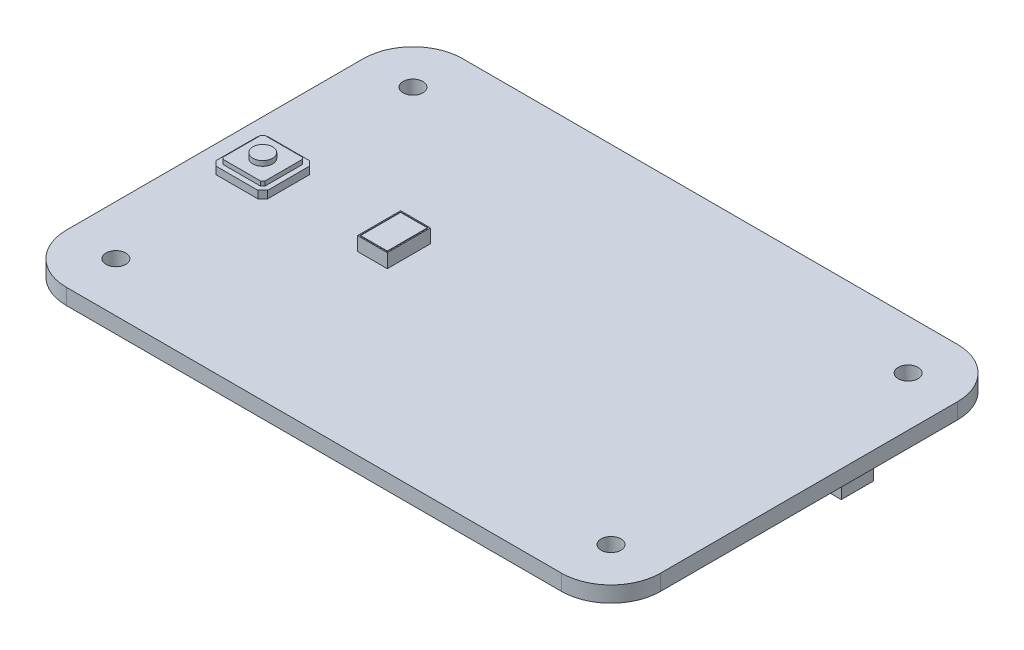
SolidWorks part; units mm, degrees
ref_plane "Front Plane" through (0, 0, 0) normal (0, 0, 1) x (1, 0, 0)
ref_plane "Top Plane" through (0, 0, 0) normal (0, 1, 0) x (1, 0, 0)
ref_plane "Right Plane" through (0, 0, 0) normal (1, 0, 0) x (0, 0, -1)
sketch "Sketch1" plane through (0, 0, 0) normal (0, 1, 0) x (1, 0, 0)
  line L1 (-30, 20) -> (30, 20)
  line L2 (-30, 20) -> (-30, -20)
  line L3 (-30, -20) -> (30, -20)
  line L4 (30, 20) -> (30, -20)
  dimension "D1" = 40
  dimension "D2" = 60
  dimension "D3" = 30
  dimension "D4" = 20
extrude "Boss-Extrude1" add sketch "Sketch1" along normal blind 1.6
sketch "Sketch2" plane through (0, 1.6, 0) normal (0, 1, 0) x (1, 0, 0)
  line L0 (-7.2175, 0) -> (11.6655, 0) construction
  line L1 (-30, 20) -> (-30, -20) construction
  line L2 (30, 20) -> (-30, 20) construction
  circle A0 centre (-25, 15) radius 1
  circle A1 centre (25, 15) radius 1
  circle A2 centre (25, -15) radius 1
  circle A3 centre (-25, -15) radius 1
  dimension "D3" = 5
  dimension "D4" = 2
  dimension "D1" = 5
  dimension "D2" = 50
extrude "Cut-Extrude1" cut sketch "Sketch2" against normal through all
fillet "Fillet1" radius 5 4 edges at (-30, 0.8, 20) (30, 0.8, 20) (30, 0.8, -20) (-30, 0.8, -20)
sketch "Sketch4" plane through (0, 1.6, 0) normal (0, 1, 0) x (1, 0, 0)
  line L0 (-31.7, 4.47) -> (-29.9, 4.47) construction
  line L1 (-29.5, 4.47) -> (-28.7, 4.47)
  line L2 (-29.5, 4.47) -> (-29.5, 4.17)
  line L3 (-29.5, 4.17) -> (-28.7, 4.17)
  line L4 (-28.7, 4.47) -> (-28.7, 4.17)
  line L5 (-31.4, 4.17) -> (-25.05, 4.17) construction
  line L7 (-29.5, 4.47) -> (-29.5, 4.17) construction
  line L8 (-28.7, 4.17) -> (-28.7, 4.47) construction
  line L9 (-25.47, 4.47) -> (-25.47, 4.17) construction
  line L10 (-25.47, 4.47) -> (-24.37, 4.47)
  line L11 (-25.47, 4.47) -> (-25.47, 4.17)
  line L12 (-25.47, 4.17) -> (-24.37, 4.17)
  line L13 (-24.37, 4.47) -> (-24.37, 4.17)
  line L14 (-24.37, 4.47) -> (-24.37, 4.17) construction
  line L15 (-30, 0) -> (-33.939, 0) construction
  line L16 (-30, 15) -> (-30, -15) construction
  line L17 (-24.37, -4.47) -> (-24.37, -4.17)
  line L18 (-25.47, -4.17) -> (-24.37, -4.17)
  line L19 (-25.47, -4.47) -> (-25.47, -4.17)
  line L20 (-25.47, -4.47) -> (-24.37, -4.47)
  line L21 (-28.7, -4.47) -> (-28.7, -4.17)
  line L22 (-29.5, -4.17) -> (-28.7, -4.17)
  line L23 (-29.5, -4.47) -> (-29.5, -4.17)
  line L24 (-29.5, -4.47) -> (-28.7, -4.47)
extrude "Cut-Extrude2" cut sketch "Sketch4" against normal through all from offset 0.5 offset against normal yes
sketch "Sketch5" plane through (0, 0, 0) normal (0, -1, 0) x (1, 0, 0)
  line L1 (-1.7, 5.7) -> (4.3, 5.7)
  line L2 (-1.7, 5.7) -> (-1.7, -5.7)
  line L3 (-1.7, -5.7) -> (4.3, -5.7)
  line L4 (4.3, 5.7) -> (4.3, -5.7)
  line L5 (-30, -15) -> (-30, 15) construction
  dimension "D1" = 11.4
  dimension "D2" = 5.7
  dimension "D3" = 6
  dimension "D4" = 34.3
extrude "Boss-Extrude2" add sketch "Sketch5" along normal blind 2 separate body
sketch "Sketch6" plane through (0, -2, 0) normal (0, -1, 0) x (1, 0, 0)
  line L0 (0, 0) -> (17.1285, 0) construction
  line L1 (3.8, 5.7) -> (3.8, 5.2)
  line L2 (4.3, 5.7) -> (-1.7, 5.7) construction
  line L3 (3.8, 5.2) -> (1.95, 5.2)
  line L4 (1.95, 5.2) -> (1.95, 4.2)
  line L5 (1.95, 4.2) -> (2.2, 4.2)
  line L6 (2.2, 4.2) -> (2.2, -4.2)
  line L7 (4.3, -5.7) -> (4.3, 5.7) construction
  line L8 (3.8, -5.7) -> (3.8, -5.2)
  line L9 (3.8, -5.2) -> (1.95, -5.2)
  line L10 (1.95, -5.2) -> (1.95, -4.2)
  line L11 (1.95, -4.2) -> (2.2, -4.2)
  line L12 (3.8, 5.2) -> (3.8, -5.2)
  line L13 (3.8649, 5.7) -> (3.8649, -5.7)
  line L14 (-1.7, -5.7) -> (4.3, -5.7) construction
  line L15 (3.8649, -5.7) -> (3.8, -5.7)
  line L16 (3.8, 5.7) -> (3.8649, 5.7)
  point P18 (2.2, 0)
  line M8 (-1.7, -5.7) -> (4.3, -5.7)
  line M10 (4.3, 5.7) -> (-1.7, 5.7)
  dimension "D1" = 0.5
  dimension "D2" = 1.85
  dimension "D3" = 1
  dimension "D4" = 0.25
  dimension "D5" = 0.5
extrude "Cut-Extrude3" cut sketch "Sketch6" against normal blind 0.5 contours L6 L0 L12 L3 L4 L5 | L0 L6 L11 L10 L9 L12 region at (2.973, -2, 2.6613) region at (2.973, -2, -2.6613)
extrude "Cut-Extrude4" cut sketch "Sketch6<3>" against normal blind 1.75 contours L12 L0 L13 L1 M10 | L0 L12 L8 L13 M8 region at (3.8325, -2, 2.85) region at (3.8325, -2, -2.85)
sketch "Sketch6<3>" plane through (0, -2, 0) normal (0, -1, 0) x (1, 0, 0) same geometry as "Sketch6"
sketch "Sketch7" plane through (0, 1.6, 0) normal (0, 1, 0) x (1, 0, 0)
  line L0 (-30, 15) -> (-30, -15) construction
  line L1 (-27.27, 2.6) -> (-23.07, 2.6)
  line L2 (-27.77, 2.1) -> (-27.77, -2.1)
  line L3 (-27.27, -2.6) -> (-23.07, -2.6)
  line L4 (-22.57, 2.1) -> (-22.57, -2.1)
  line L5 (-27.77, 2.6) -> (-22.57, -2.6) construction
  line L6 (-27.77, -2.6) -> (-22.57, 2.6) construction
  line L8 (-27.77, 2.1) -> (-27.27, 2.6)
  line L9 (-23.07, 2.6) -> (-22.57, 2.1)
  line L10 (-22.57, -2.1) -> (-23.07, -2.6)
  line L11 (-27.77, -2.1) -> (-27.27, -2.6)
  point P0 (-25.17, 0)
  dimension "D1" = 4.83
  dimension "D2" = 5.2
  dimension "D3" = 5.2
extrude "Boss-Extrude3" add sketch "Sketch7" along normal blind 0.75 separate body
sketch "Sketch8" plane through (0, 2.35, 0) normal (0, 1, 0) x (1, 0, 0)
  line L8 (-25.17, 2.1) -> (-25.17, -1.5934) construction
  line L16 (-27.0629, 2.1) -> (-27.27, 1.8929)
  line L17 (-27.27, 1.8929) -> (-27.27, -1.8929)
  line L18 (-27.27, -1.8929) -> (-27.0629, -2.1)
  line L19 (-27.0629, -2.1) -> (-23.2771, -2.1)
  line L20 (-23.2771, -2.1) -> (-23.07, -1.8929)
  line L21 (-23.07, -1.8929) -> (-23.07, 1.8929)
  line L22 (-23.07, 1.8929) -> (-23.2771, 2.1)
  line L23 (-23.2771, 2.1) -> (-27.0629, 2.1)
  line L24 (-27.0629, 2.1) -> (-27.27, 1.8929)
  line L25 (-27.27, 1.8929) -> (-27.27, -1.8929)
  line L26 (-27.27, -1.8929) -> (-27.0629, -2.1)
  line L27 (-27.0629, -2.1) -> (-23.2771, -2.1)
  line L28 (-23.2771, -2.1) -> (-23.07, -1.8929)
  line L29 (-23.07, -1.8929) -> (-23.07, 1.8929)
  line L30 (-23.07, 1.8929) -> (-23.2771, 2.1)
  line L31 (-23.2771, 2.1) -> (-27.0629, 2.1)
  circle A0 centre (-25.17, 0) radius 1
  dimension "D2" = 2
  dimension "D1" = 0.5
extrude "Boss-Extrude4" add sketch "Sketch8" along normal blind 0.45 contours L30 L31 A0 L24 L25 L26 L27 L28 L29 | A0 region at (-25.17, 2.35, -2.0406)
sketch "Sketch9" plane through (0, 1.6, 0) normal (0, 1, 0) x (1, 0, 0)
  line L1 (-13.42, 2.175) -> (-10.42, 2.175)
  line L2 (-13.42, 2.175) -> (-13.42, -2.175)
  line L3 (-13.42, -2.175) -> (-10.42, -2.175)
  line L4 (-10.42, 2.175) -> (-10.42, -2.175)
  line L5 (-13.42, 2.175) -> (-10.42, -2.175) construction
  line L6 (-13.42, -2.175) -> (-10.42, 2.175) construction
  line L7 (-22.57, -2.1) -> (-22.57, 2.1) construction
  point P0 (-11.92, 0)
  dimension "D1" = 4.35
  dimension "D2" = 3
  dimension "D3" = 9.15
extrude "Boss-Extrude6" add sketch "Sketch9" along normal blind 1.4 separate body
sketch "Sketch10" plane through (0, 3, 0) normal (0, 1, 0) x (1, 0, 0)
  line L8 (-10.52, -2.075) -> (-10.52, 2.075)
  line L9 (-10.52, 2.075) -> (-13.32, 2.075)
  line L10 (-13.32, 2.075) -> (-13.32, -2.075)
  line L11 (-13.32, -2.075) -> (-10.52, -2.075)
  line L12 (-10.52, -2.075) -> (-10.52, 2.075)
  line L13 (-10.52, 2.075) -> (-13.32, 2.075)
  line L14 (-13.32, 2.075) -> (-13.32, -2.075)
  line L15 (-13.32, -2.075) -> (-10.52, -2.075)
  dimension "D1" = 0.1
extrude "Cut-Extrude5" cut sketch "Sketch10" against normal blind 0.1
sketch "Sketch11" plane through (0, 2.9, 0) normal (0, 1, 0) x (1, 0, 0)
  line L8 (-13.27, -2.025) -> (-10.57, -2.025)
  line L9 (-10.57, -2.025) -> (-10.57, 2.025)
  line L10 (-10.57, 2.025) -> (-13.27, 2.025)
  line L11 (-13.27, 2.025) -> (-13.27, -2.025)
  line L12 (-13.27, -2.025) -> (-10.57, -2.025)
  line L13 (-10.57, -2.025) -> (-10.57, 2.025)
  line L14 (-10.57, 2.025) -> (-13.27, 2.025)
  line L15 (-13.27, 2.025) -> (-13.27, -2.025)
  dimension "D1" = 0.05
extrude "Boss-Extrude7" add sketch "Sketch11" along normal blind 0.1
sketch "Sketch13" plane through (0, 0, 0) normal (0, -1, 0) x (1, 0, 0)
  line L0 (25, -20) -> (-25, -20) construction
  line L1 (-16.5, -15) -> (-12.5, -15)
  line L2 (-16.5, -15) -> (-16.5, -19)
  line L3 (-16.5, -19) -> (-12.5, -19)
  line L4 (-12.5, -15) -> (-12.5, -19)
  line L5 (-16.5, -15) -> (-12.5, -19) construction
  line L6 (-16.5, -19) -> (-12.5, -15) construction
  line L7 (-30, -15) -> (-30, 15) construction
  point P0 (-14.5, -17)
  dimension "D1" = 4
  dimension "D2" = 4
  dimension "D3" = 1
  dimension "D4" = 17.5
extrude "Boss-Extrude8" add sketch "Sketch13" along normal blind 1.75 separate body
sketch "Sketch14" plane through (0, 0, 0) normal (0, -1, 0) x (1, 0, 0)
  line L0 (4.3, -5.7) -> (4.3, 5.7) construction
  line L1 (-0.65, -9.7) -> (4.55, -9.7)
  line L2 (-0.65, -9.7) -> (-0.65, -15.1)
  line L3 (-0.65, -15.1) -> (4.55, -15.1)
  line L4 (4.55, -9.7) -> (4.55, -15.1)
  line L5 (-1.7, -5.7) -> (3.8, -5.7) construction
  dimension "D1" = 0.25
  dimension "D2" = 5.4
  dimension "D3" = 5.2
  dimension "D4" = 4
extrude "Boss-Extrude9" add sketch "Sketch14" along normal blind 1.5 separate body
sketch "Sketch15" plane through (0, 0, 0) normal (0, -1, 0) x (1, 0, 0)
  line L0 (4.3, -5.7) -> (4.3, 5.7) construction
  line L1 (-9.2, 13.5) -> (-5.4, 13.5)
  line L2 (-9.2, 13.5) -> (-9.2, 8.5)
  line L3 (-9.2, 8.5) -> (-5.4, 8.5)
  line L4 (-5.4, 13.5) -> (-5.4, 8.5)
  line L5 (-1.7, -5.7) -> (3.8, -5.7) construction
  dimension "D1" = 3.8
  dimension "D2" = 5
  dimension "D3" = 13.5
  dimension "D4" = 19.2
extrude "Boss-Extrude10" add sketch "Sketch15" along normal blind 1.5 separate body
sketch "Sketch16" plane through (0, 0, 0) normal (0, -1, 0) x (1, 0, 0)
  line L0 (30, 15) -> (30, -15) construction
  line L1 (28.1, -3.5) -> (29.75, -3.5)
  line L2 (28.1, -3.5) -> (28.1, -6.75)
  line L3 (28.1, -6.75) -> (29.75, -6.75)
  line L4 (29.75, -3.5) -> (29.75, -6.75)
  line L5 (25, -20) -> (-25, -20) construction
  dimension "D1" = 0.25
  dimension "D2" = 1.65
  dimension "D3" = 3.25
  dimension "D4" = 13.25
extrude "Boss-Extrude11" add sketch "Sketch16" along normal blind 1.35 separate body
sketch "Sketch17" plane through (0, 2.8, 0) normal (0, 1, 0) x (1, 0, 0)
  line L1 (-25.17, 2.1) -> (-25.17, -2.1) construction
  line L2 (-23.2771, 2.1) -> (-27.0629, 2.1) construction
  line L3 (-27.0629, -2.1) -> (-23.2771, -2.1) construction
  line L4 (-27.27, 0) -> (-23.07, 0) construction
  line L5 (-27.27, 1.8929) -> (-27.27, -1.8929) construction
  line L6 (-23.07, -1.8929) -> (-23.07, 1.8929) construction
  circle A0 centre (-25.17, 0) radius 1
  dimension "D1" = 2
extrude "Boss-Extrude12" add sketch "Sketch17" along normal blind 0.5
sketch "Sketch18" plane through (0, 3.3, 0) normal (0, 1, 0) x (1, 0, 0)
  line L0 (-25.17, 0) -> (-27.3592, 2.1092) construction
sketch "Sketch19" plane through (0, 0, 0) normal (0, -1, 0) x (1, 0, 0)
  line L1 (-29.2, 7.17) -> (-28.3, 7.17)
  line L2 (-29.2, 7.17) -> (-29.2, 5.47)
  line L3 (-29.2, 5.47) -> (-28.3, 5.47)
  line L4 (-28.3, 7.17) -> (-28.3, 5.47)
  line L5 (-27.7, 7.17) -> (-26.8, 7.17)
  line L6 (-27.7, 7.17) -> (-27.7, 5.47)
  line L7 (-27.7, 5.47) -> (-26.8, 5.47)
  line L8 (-26.8, 7.17) -> (-26.8, 5.47)
  line L9 (-30, -15) -> (-30, 15) construction
  line L10 (-19.0449, 0) -> (-46.6157, 0) construction
  line L11 (-27.7, -5.47) -> (-26.8, -5.47)
  line L12 (-26.8, -7.17) -> (-26.8, -5.47)
  line L13 (-27.7, -7.17) -> (-26.8, -7.17)
  line L14 (-27.7, -7.17) -> (-27.7, -5.47)
  line L15 (-29.2, -5.47) -> (-28.3, -5.47)
  line L16 (-28.3, -7.17) -> (-28.3, -5.47)
  line L17 (-29.2, -7.17) -> (-28.3, -7.17)
  line L18 (-29.2, -7.17) -> (-29.2, -5.47)
  line L19 (-29.5, 4.47) -> (-28.7, 4.47) construction
  line L20 (-29.5, 4.32) -> (-32.4644, 4.32) construction
  line L21 (-29.5, 4.17) -> (-29.5, 4.47) construction
  dimension "D1" = 1.7
  dimension "D2" = 1.7
  dimension "D3" = 0.9
  dimension "D4" = 0.9
  dimension "D5" = 1
  dimension "D6" = 0.6
  dimension "D7" = 0.8
extrude "Boss-Extrude13" add sketch "Sketch19" along normal blind 0.15 separate body
sketch "Sketch20" plane through (0, -0.15, 0) normal (0, -1, 0) x (1, 0, 0)
  line L0 (-29.2, 7.17) -> (-29.2, 5.47) construction
  line L1 (-29.2, 6.92) -> (-28.3, 6.92)
  line L2 (-29.2, 6.92) -> (-29.2, 5.72)
  line L3 (-29.2, 5.72) -> (-28.3, 5.72)
  line L4 (-28.3, 6.92) -> (-28.3, 5.72)
  line L5 (-28.3, 5.47) -> (-28.3, 7.17) construction
  line L6 (-27.7, 7.17) -> (-27.7, 5.47) construction
  line L7 (-27.7, 6.92) -> (-26.8, 6.92)
  line L8 (-27.7, 6.92) -> (-27.7, 5.72)
  line L9 (-27.7, 5.72) -> (-26.8, 5.72)
  line L10 (-26.8, 6.92) -> (-26.8, 5.72)
  line L11 (-26.8, 5.47) -> (-26.8, 7.17) construction
  line L12 (-28.3, 7.17) -> (-29.2, 7.17) construction
  line L13 (0, 0) -> (-19.5749, 0) construction
  line L14 (-27.7, -5.72) -> (-26.8, -5.72)
  line L15 (-26.8, -6.92) -> (-26.8, -5.72)
  line L16 (-27.7, -6.92) -> (-26.8, -6.92)
  line L17 (-27.7, -6.92) -> (-27.7, -5.72)
  line L18 (-29.2, -5.72) -> (-28.3, -5.72)
  line L19 (-28.3, -6.92) -> (-28.3, -5.72)
  line L20 (-29.2, -6.92) -> (-28.3, -6.92)
  line L21 (-29.2, -6.92) -> (-29.2, -5.72)
  dimension "D1" = 1.2
  dimension "D2" = 0.25
extrude "Boss-Extrude14" add sketch "Sketch20" along normal blind 0.25
